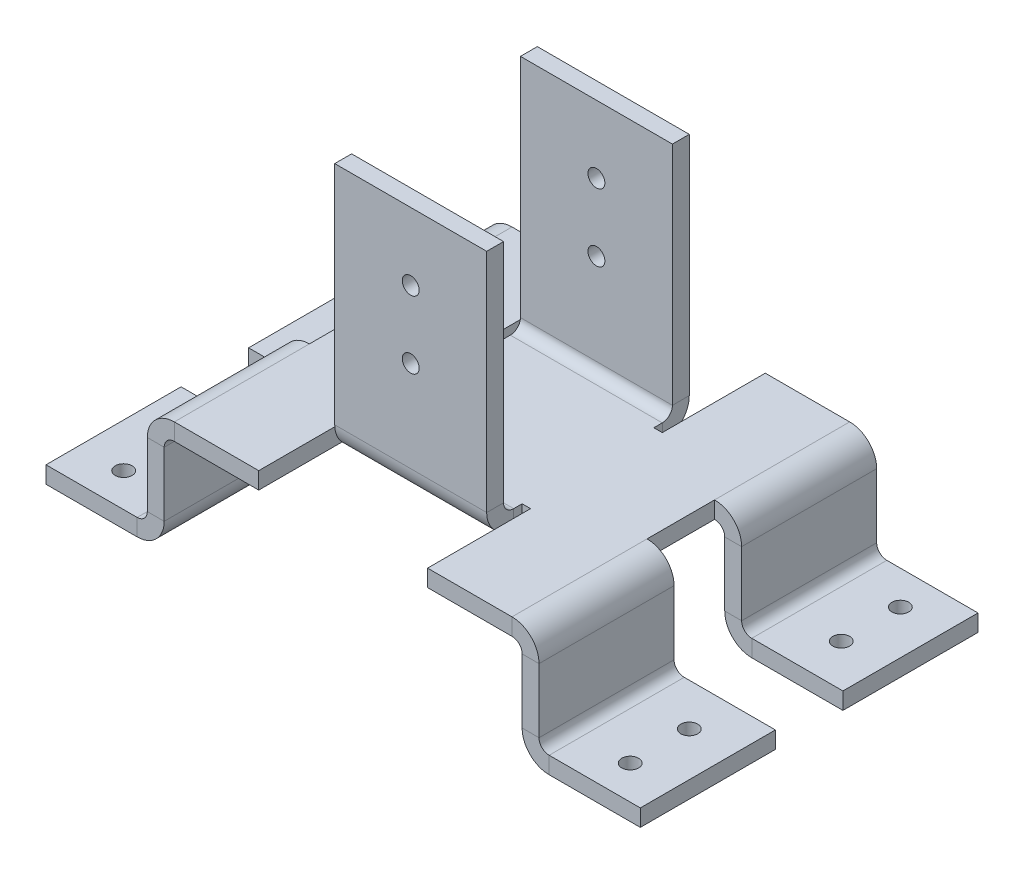
SolidWorks part; units mm, degrees
note: The reader was unsure of these and kept them because the rebuilt part matched: flange length of "边线-法兰1", "边线-法兰2", "边线-法兰14", "边线-法兰15", "边线-法兰16", "边线-法兰17", "边线-法兰18", "边线-法兰19", "边线-法兰20", "边线-法兰21".
ref_plane "前视基准面" through (0, 0, 0) normal (0, 0, 1) x (1, 0, 0)
ref_plane "上视基准面" through (0, 0, 0) normal (0, 1, 0) x (1, 0, 0)
ref_plane "右视基准面" through (0, 0, 0) normal (1, 0, 0) x (0, 0, -1)
other "Configuration Table"
sketch "草图1" plane through (0, 0, 0) normal (0, 1, 0) x (1, 0, 0)
  line L0 (-25, -25) -> (-25, -50)
  line L5 (-50, -50) -> (50, -50) construction
  line L6 (-50, -50) -> (-50, 50)
  line L11 (-50, 50) -> (50, 50) construction
  line L12 (50, -50) -> (50, 50)
  line L13 (-50, -50) -> (50, 50) construction
  line L14 (-50, 50) -> (50, -50) construction
  line L15 (-25, -25) -> (25, -25)
  line L16 (-25, -25) -> (-25, 25) construction
  line L17 (-25, 25) -> (25, 25)
  line L18 (25, -25) -> (25, 25) construction
  line L19 (-25, -25) -> (25, 25) construction
  line L20 (-25, 25) -> (25, -25) construction
  line L21 (-25, -50) -> (-50, -50)
  line L22 (25, -25) -> (25, -50)
  line L23 (25, -50) -> (50, -50)
  line L24 (-25, 25) -> (-25, 50)
  line L25 (-25, 50) -> (-50, 50)
  line L26 (25, 25) -> (25, 50)
  line L27 (25, 50) -> (50, 50)
  point P0 (0, 0)
  point P6 (0, 0)
  dimension "D1" = 100
  dimension "D2" = 100
  dimension "D3" = 50
base flange "基体-法兰1" sketch "草图1" thickness 5 reverse thickness direction no parameters "D1"=0.7366
edge flange "边线-法兰1" sketch "草图8" flange angle 90 flange length 75 flange position material outside bend radius 3 thickness 5 relief rectangular parameters "D6"=10
sketch "草图8" plane through (0, 0, -25) normal (0, 0, -1) x (-1, 0, 0)
  line L1 (-22.5, 0) -> (22.5, 0)
  line L2 (-22.5, 0) -> (-22.5, 70)
  line L3 (-22.5, 70) -> (22.5, 70)
  line L4 (22.5, 0) -> (22.5, 70)
  line L5 (-25, 0) -> (25, 0) construction
  point P6 (0, 70)
  dimension "D1" = 70
  dimension "D2" = 45
bend "边线折弯1" bend radius 3 bend angle 90 parameters "D5"=1
edge flange "边线-法兰2" sketch "草图11" flange angle 90 flange length 75 flange position material outside bend radius 3 thickness 5 relief rectangular parameters "D6"=10
sketch "草图11" plane through (0, 0, 25) normal (0, 0, 1) x (1, 0, 0)
  line L6 (-22.5, 70) -> (22.5, 70)
  line L7 (-22.5, 70) -> (-22.5, 0)
  line L8 (-22.5, 0) -> (22.5, 0)
  line L9 (22.5, 70) -> (22.5, 0)
bend "边线折弯2" bend radius 3 bend angle 90 parameters "D5"=2
edge flange "边线-法兰14" sketch "草图54" flange angle 90 flange length 35 flange position bend outside bend radius 3 thickness 5 relief rectangular parameters "D6"=10
sketch "草图54" plane through (50, -5, 0) normal (1, 0, 0) x (0, 0, 1)
  line L6 (50, 0) -> (10, 0)
  line L7 (50, 0) -> (50, 30)
  line L8 (50, 30) -> (10, 30)
  line L9 (10, 0) -> (10, 30)
  dimension "D1" = 30
  dimension "D2" = 40
bend "边线折弯12" bend radius 3 bend angle 90 parameters "D5"=3
edge flange "边线-法兰15" sketch "草图57" flange angle 90 flange length 35 flange position bend outside bend radius 3 thickness 5 relief rectangular parameters "D6"=10
sketch "草图57" plane through (50, -5, 0) normal (1, 0, 0) x (0, 0, 1)
  line L6 (-50, 0) -> (-10, 0)
  line L7 (-50, 0) -> (-50, 30)
  line L8 (-50, 30) -> (-10, 30)
  line L9 (-10, 0) -> (-10, 30)
  dimension "D1" = 40
  dimension "D2" = 30
bend "边线折弯13" bend radius 3 bend angle 90 parameters "D5"=4
edge flange "边线-法兰16" sketch "草图62" flange angle 90 flange length 35 flange position bend outside bend radius 3 thickness 5 relief rectangular parameters "D6"=10
sketch "草图62" plane through (-50, -5, 0) normal (-1, 0, 0) x (0, 0, -1)
  line L6 (50, 0) -> (10, 0)
  line L7 (50, 0) -> (50, 30)
  line L8 (50, 30) -> (10, 30)
  line L9 (10, 0) -> (10, 30)
bend "边线折弯14" bend radius 3 bend angle 90 parameters "D5"=5
edge flange "边线-法兰17" sketch "草图65" flange angle 90 flange length 35 flange position bend outside bend radius 3 thickness 5 relief rectangular parameters "D6"=10
sketch "草图65" plane through (-50, -5, 0) normal (-1, 0, 0) x (0, 0, -1)
  line L6 (-50, 0) -> (-10, 0)
  line L7 (-50, 0) -> (-50, 30)
  line L8 (-50, 30) -> (-10, 30)
  line L9 (-10, 0) -> (-10, 30)
bend "边线折弯15" bend radius 3 bend angle 90 parameters "D5"=6
edge flange "边线-法兰18" sketch "草图70" flange angle 90 flange length 35 bend radius 3 thickness 5 relief rectangular parameters "D6"=10
sketch "草图70" plane through (-58, -35, 0) normal (0, -1, 0) x (0, 0, 1)
  line L0 (-50, 0) -> (-10, 0) construction
  line L1 (-50, 0) -> (-10, 0)
  line L2 (-50, 0) -> (-50, 30)
  line L3 (-50, 30) -> (-10, 30)
  line L4 (-10, 30) -> (-10, 0)
  dimension "D1" = 30
bend "边线折弯16" bend radius 3 bend angle 90 parameters "D5"=7
edge flange "边线-法兰19" sketch "草图73" flange angle 90 flange length 35 bend radius 3 thickness 5 relief rectangular parameters "D6"=10
sketch "草图73" plane through (-58, -35, 0) normal (0, -1, 0) x (0, 0, 1)
  line L0 (10, 0) -> (50, 0) construction
  line L1 (10, 0) -> (50, 0)
  line L2 (10, 0) -> (10, 30)
  line L3 (10, 30) -> (50, 30)
  line L4 (50, 30) -> (50, 0)
  dimension "D1" = 30
bend "边线折弯17" bend radius 3 bend angle 90 parameters "D5"=8
edge flange "边线-法兰20" sketch "草图76" flange angle 90 flange length 35 bend radius 3 thickness 5 relief rectangular parameters "D6"=10
sketch "草图76" plane through (58, -35, 0) normal (0, -1, 0) x (0, 0, -1)
  line L0 (-50, 0) -> (-10, 0) construction
  line L1 (-50, 0) -> (-10, 0)
  line L2 (-50, 0) -> (-50, 30)
  line L3 (-50, 30) -> (-10, 30)
  line L4 (-10, 30) -> (-10, 0)
  dimension "D1" = 30
bend "边线折弯18" bend radius 3 bend angle 90 parameters "D5"=9
edge flange "边线-法兰21" sketch "草图79" flange angle 90 flange length 35 bend radius 3 thickness 5 relief rectangular parameters "D6"=10
sketch "草图79" plane through (58, -35, 0) normal (0, -1, 0) x (0, 0, -1)
  line L0 (10, 0) -> (50, 0) construction
  line L1 (10, 0) -> (50, 0)
  line L2 (10, 0) -> (10, 30)
  line L3 (10, 30) -> (50, 30)
  line L4 (50, 30) -> (50, 0)
  dimension "D1" = 30
bend "边线折弯19" bend radius 3 bend angle 90 parameters "D5"=10
sketch "草图80" plane through (0, 0, 0) normal (0, 1, 0) x (1, 0, 0)
  line L1 (-75, -40) -> (75, -40) construction
  line L2 (-75, -40) -> (-75, 40) construction
  line L3 (-75, 40) -> (75, 40) construction
  line L4 (75, -40) -> (75, 40) construction
  line L5 (-75, -40) -> (75, 40) construction
  line L6 (-75, 40) -> (75, -40) construction
  circle A0 centre (-75, 40) radius 2.5
  circle A1 centre (75, 40) radius 2.5
  circle A2 centre (-75, -40) radius 2.5
  circle A3 centre (75, -40) radius 2.5
  point P0 (0, 0)
  dimension "D3" = 5
  dimension "D4" = 5
  dimension "D5" = 5
  dimension "D6" = 5
  dimension "D1" = 80
  dimension "D2" = 150
extrude "切除-拉伸1" cut sketch "草图80" along normal up to surface (5 mm away) from surface at -35 up to face at (-74.5, -30, -30) starting at face at (-74.5, -35, -30)
sketch "草图83" plane through (0, 0, 0) normal (0, 0, 1) x (1, 0, 0)
  line L1 (-22.5, 70) -> (22.5, 70) construction
  line L2 (-22.5, 70) -> (-22.5, 10) construction
  line L3 (-22.5, 10) -> (22.5, 10) construction
  line L4 (22.5, 70) -> (22.5, 10) construction
  line L5 (-22.5, 70) -> (22.5, 10) construction
  line L6 (22.5, 70) -> (-22.5, 10) construction
  line L7 (0, 30) -> (0, 50) construction
  circle A0 centre (0, 50) radius 2.5
  circle A1 centre (0, 30) radius 2.5
  point P11 (0, 40)
  dimension "D3" = 5
  dimension "D4" = 5
  dimension "D1" = 60
  dimension "D2" = 20
extrude "切除-拉伸3" cut sketch "草图83" against normal through all and the other way through all normal cut yes
sketch "草图84" plane through (0, 0, 0) normal (0, 1, 0) x (1, 0, 0)
  line L1 (-75, -22.5) -> (75, -22.5) construction
  line L2 (-75, -22.5) -> (-75, 22.5) construction
  line L3 (-75, 22.5) -> (75, 22.5) construction
  line L4 (75, -22.5) -> (75, 22.5) construction
  line L5 (-75, -22.5) -> (75, 22.5) construction
  line L6 (-75, 22.5) -> (75, -22.5) construction
  circle A0 centre (75, 22.5) radius 2.5
  circle A1 centre (75, -22.5) radius 2.5
  circle A2 centre (-75, -22.5) radius 2.5
  circle A3 centre (-75, 22.5) radius 2.5
  point P0 (0, 0)
  dimension "D3" = 5
  dimension "D4" = 5
  dimension "D5" = 5
  dimension "D6" = 5
  dimension "D1" = 150
  dimension "D2" = 45
extrude "切除-拉伸5" cut sketch "草图84" against normal up to surface (5 mm away) from surface at -30 up to face at (-75, -35, 42.5) starting at face at (-75, -30, 42.5)
sketch "折弯-线1" plane through (0, 0, 0) normal (0, 1, 0) x (1, 0, 0)
sketch "边界框1" plane through (0, 0, 0) normal (0, 1, 0) x (1, 0, 0)
sheet metal parameters "钣金6" thickness 5 parameters "D1"=0.7366
flat pattern "平板型式6" [suppressed]
sketch "折弯-线2" plane through (0, 0, 0) normal (0, 1, 0) x (1, 0, 0)
sketch "边界框2" [suppressed] plane through (0, 0, 0) normal (0, 1, 0) x (1, 0, 0)
sheet metal parameters "钣金7" thickness 5 parameters "D1"=0.7366
flat pattern "平板型式6" [suppressed]
sketch "折弯-线2" plane through (0, 0, 0) normal (0, 1, 0) x (1, 0, 0)
sketch "边界框2" [suppressed] plane through (0, 0, 0) normal (0, 1, 0) x (1, 0, 0)
bend of the flat pattern "展平-<边线折弯1>1"
sheet metal parameters "钣金8" thickness 5 parameters "D1"=0.7366
flat pattern "平板型式6" [suppressed]
sketch "折弯-线2" plane through (0, 0, 0) normal (0, 1, 0) x (1, 0, 0)
sketch "边界框2" [suppressed] plane through (0, 0, 0) normal (0, 1, 0) x (1, 0, 0)
bend of the flat pattern "展平-<边线折弯1>1"
bend of the flat pattern "展平-<边线折弯2>1"
sheet metal parameters "钣金18" thickness 5 parameters "D1"=0.7366
flat pattern "平板型式6" [suppressed]
sketch "折弯-线2" plane through (0, 0, 0) normal (0, 1, 0) x (1, 0, 0)
sketch "边界框2" [suppressed] plane through (0, 0, 0) normal (0, 1, 0) x (1, 0, 0)
bend of the flat pattern "展平-<边线折弯1>1"
bend of the flat pattern "展平-<边线折弯2>1"
bend of the flat pattern "展平-<边线折弯12>1"
sheet metal parameters "钣金19" thickness 5 parameters "D1"=0.7366
flat pattern "平板型式6" [suppressed]
sketch "折弯-线2" plane through (0, 0, 0) normal (0, 1, 0) x (1, 0, 0)
sketch "边界框2" [suppressed] plane through (0, 0, 0) normal (0, 1, 0) x (1, 0, 0)
bend of the flat pattern "展平-<边线折弯1>1"
bend of the flat pattern "展平-<边线折弯2>1"
bend of the flat pattern "展平-<边线折弯13>1"
bend of the flat pattern "展平-<边线折弯12>1"
sheet metal parameters "钣金20" thickness 5 parameters "D1"=0.7366
flat pattern "平板型式6" [suppressed]
sketch "折弯-线2" plane through (0, 0, 0) normal (0, 1, 0) x (1, 0, 0)
sketch "边界框2" [suppressed] plane through (0, 0, 0) normal (0, 1, 0) x (1, 0, 0)
bend of the flat pattern "展平-<边线折弯1>1"
bend of the flat pattern "展平-<边线折弯2>1"
bend of the flat pattern "展平-<边线折弯13>1"
bend of the flat pattern "展平-<边线折弯14>1"
bend of the flat pattern "展平-<边线折弯12>1"
sheet metal parameters "钣金21" thickness 5 parameters "D1"=0.7366
flat pattern "平板型式6" [suppressed]
sketch "折弯-线2" plane through (0, 0, 0) normal (0, 1, 0) x (1, 0, 0)
sketch "边界框2" [suppressed] plane through (0, 0, 0) normal (0, 1, 0) x (1, 0, 0)
bend of the flat pattern "展平-<边线折弯1>1"
bend of the flat pattern "展平-<边线折弯2>1"
bend of the flat pattern "展平-<边线折弯13>1"
bend of the flat pattern "展平-<边线折弯14>1"
bend of the flat pattern "展平-<边线折弯15>1"
bend of the flat pattern "展平-<边线折弯12>1"
sheet metal parameters "钣金22" thickness 5 parameters "D1"=0.7366
flat pattern "平板型式6" [suppressed]
sketch "折弯-线2" plane through (0, 0, 0) normal (0, 1, 0) x (1, 0, 0)
sketch "边界框2" [suppressed] plane through (0, 0, 0) normal (0, 1, 0) x (1, 0, 0)
bend of the flat pattern "展平-<边线折弯1>1"
bend of the flat pattern "展平-<边线折弯2>1"
bend of the flat pattern "展平-<边线折弯13>1"
bend of the flat pattern "展平-<边线折弯14>1"
bend of the flat pattern "展平-<边线折弯15>1"
bend of the flat pattern "展平-<边线折弯12>1"
bend of the flat pattern "展平-<边线折弯16>1"
sheet metal parameters "钣金23" thickness 5 parameters "D1"=0.7366
flat pattern "平板型式6" [suppressed]
sketch "折弯-线2" plane through (0, 0, 0) normal (0, 1, 0) x (1, 0, 0)
sketch "边界框2" [suppressed] plane through (0, 0, 0) normal (0, 1, 0) x (1, 0, 0)
bend of the flat pattern "展平-<边线折弯1>1"
bend of the flat pattern "展平-<边线折弯2>1"
bend of the flat pattern "展平-<边线折弯13>1"
bend of the flat pattern "展平-<边线折弯14>1"
bend of the flat pattern "展平-<边线折弯15>1"
bend of the flat pattern "展平-<边线折弯12>1"
bend of the flat pattern "展平-<边线折弯17>1"
bend of the flat pattern "展平-<边线折弯16>1"
sheet metal parameters "钣金24" thickness 5 parameters "D1"=0.7366
flat pattern "平板型式6" [suppressed]
sketch "折弯-线2" plane through (0, 0, 0) normal (0, 1, 0) x (1, 0, 0)
sketch "边界框2" [suppressed] plane through (0, 0, 0) normal (0, 1, 0) x (1, 0, 0)
bend of the flat pattern "展平-<边线折弯1>1"
bend of the flat pattern "展平-<边线折弯2>1"
bend of the flat pattern "展平-<边线折弯13>1"
bend of the flat pattern "展平-<边线折弯14>1"
bend of the flat pattern "展平-<边线折弯15>1"
bend of the flat pattern "展平-<边线折弯12>1"
bend of the flat pattern "展平-<边线折弯17>1"
bend of the flat pattern "展平-<边线折弯18>1"
bend of the flat pattern "展平-<边线折弯16>1"
sheet metal parameters "钣金25" thickness 5 parameters "D1"=0.7366
flat pattern "平板型式6" [suppressed]
sketch "折弯-线2" plane through (0, 0, 0) normal (0, 1, 0) x (1, 0, 0)
sketch "边界框2" [suppressed] plane through (0, 0, 0) normal (0, 1, 0) x (1, 0, 0)
bend of the flat pattern "展平-<边线折弯1>1"
bend of the flat pattern "展平-<边线折弯2>1"
bend of the flat pattern "展平-<边线折弯13>1"
bend of the flat pattern "展平-<边线折弯14>1"
bend of the flat pattern "展平-<边线折弯15>1"
bend of the flat pattern "展平-<边线折弯12>1"
bend of the flat pattern "展平-<边线折弯17>1"
bend of the flat pattern "展平-<边线折弯18>1"
bend of the flat pattern "展平-<边线折弯19>1"
bend of the flat pattern "展平-<边线折弯16>1"
sheet metal parameters "钣金26" thickness 5 parameters "D1"=0.7366
flat pattern "平板型式6" [suppressed]
sketch "折弯-线2" plane through (0, 0, 0) normal (0, 1, 0) x (1, 0, 0)
sketch "边界框2" [suppressed] plane through (0, 0, 0) normal (0, 1, 0) x (1, 0, 0)
bend of the flat pattern "展平-<边线折弯1>1"
bend of the flat pattern "展平-<边线折弯2>1"
bend of the flat pattern "展平-<边线折弯13>1"
bend of the flat pattern "展平-<边线折弯14>1"
bend of the flat pattern "展平-<边线折弯15>1"
bend of the flat pattern "展平-<边线折弯12>1"
bend of the flat pattern "展平-<边线折弯17>1"
bend of the flat pattern "展平-<边线折弯18>1"
bend of the flat pattern "展平-<边线折弯19>1"
bend of the flat pattern "展平-<边线折弯16>1"
sheet metal parameters "钣金28" thickness 5 parameters "D1"=0.7366
flat pattern "平板型式6" [suppressed]
sketch "折弯-线2" plane through (0, 0, 0) normal (0, 1, 0) x (1, 0, 0)
sketch "边界框2" [suppressed] plane through (0, 0, 0) normal (0, 1, 0) x (1, 0, 0)
bend of the flat pattern "展平-<边线折弯1>1"
bend of the flat pattern "展平-<边线折弯2>1"
bend of the flat pattern "展平-<边线折弯13>1"
bend of the flat pattern "展平-<边线折弯14>1"
bend of the flat pattern "展平-<边线折弯15>1"
bend of the flat pattern "展平-<边线折弯12>1"
bend of the flat pattern "展平-<边线折弯17>1"
bend of the flat pattern "展平-<边线折弯18>1"
bend of the flat pattern "展平-<边线折弯19>1"
bend of the flat pattern "展平-<边线折弯16>1"
sheet metal parameters "钣金29" thickness 5 parameters "D1"=0.7366
flat pattern "平板型式6" [suppressed]
sketch "折弯-线2" plane through (0, 0, 0) normal (0, 1, 0) x (1, 0, 0)
sketch "边界框2" [suppressed] plane through (0, 0, 0) normal (0, 1, 0) x (1, 0, 0)
bend of the flat pattern "展平-<边线折弯1>1"
bend of the flat pattern "展平-<边线折弯2>1"
bend of the flat pattern "展平-<边线折弯13>1"
bend of the flat pattern "展平-<边线折弯14>1"
bend of the flat pattern "展平-<边线折弯15>1"
bend of the flat pattern "展平-<边线折弯12>1"
bend of the flat pattern "展平-<边线折弯17>1"
bend of the flat pattern "展平-<边线折弯18>1"
bend of the flat pattern "展平-<边线折弯19>1"
bend of the flat pattern "展平-<边线折弯16>1"
